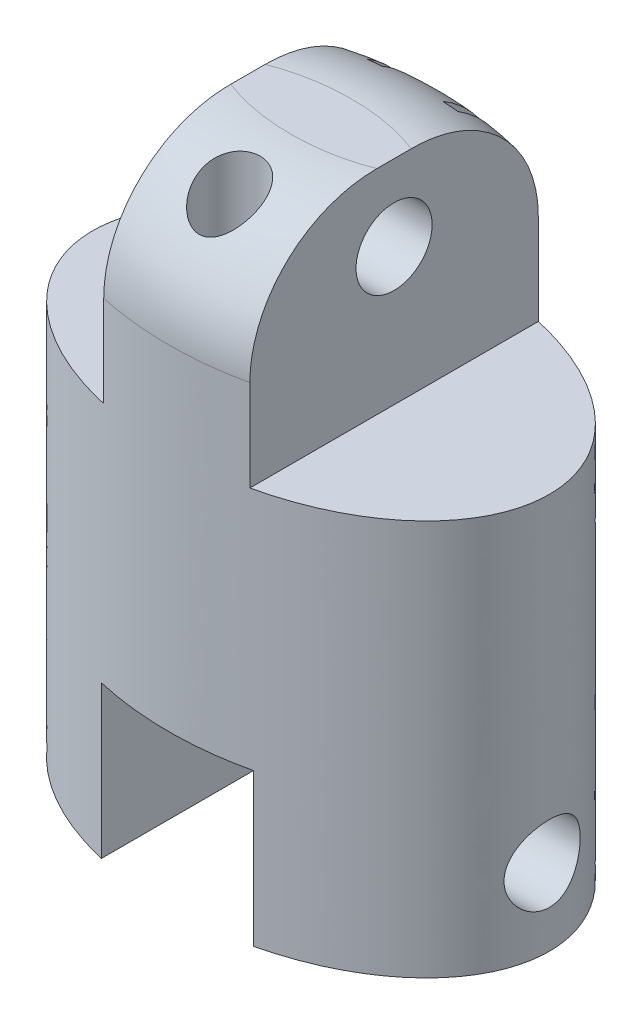
SolidWorks part; units mm, degrees
ref_plane "Front Plane" through (0, 0, 0) normal (0, 0, 1) x (1, 0, 0)
ref_plane "Top Plane" through (0, 0, 0) normal (0, 1, 0) x (1, 0, 0)
ref_plane "Right Plane" through (0, 0, 0) normal (1, 0, 0) x (0, 0, -1)
sketch "Sketch1" plane through (0, 0, 0) normal (0, 1, 0) x (1, 0, 0)
  circle A0 centre (0, -3.81) radius 1.27
  ellipse E0 centre (0, 0) end of major axis (-9.525, 0) minor radius 6.35
  dimension "D3" = 2.54
  dimension "D4" = 2.54
  dimension "D1" = 12.7
  dimension "D2" = 19.05
extrude "Boss-Extrude1" add sketch "Sketch1" along normal blind 25.4
sketch "Sketch2" plane through (0, 0, 0) normal (0, 0, 1) x (1, 0, 0)
  line L0 (-9.525, 12.7) -> (9.525, 12.7) construction
  line L1 (-9.525, 25.4) -> (-9.525, 0) construction
  line L2 (9.525, 0) -> (9.525, 25.4) construction
  line L3 (0, 25.4) -> (0, 0) construction
  line L4 (1.27, 25.4) -> (-1.27, 25.4) construction
  line L5 (9.525, 25.4) -> (-9.525, 25.4) construction
  line L10 (3.048, 16.51) -> (3.048, 25.4)
  line L11 (-3.175, 0) -> (3.175, 0)
  line L12 (-3.048, 16.51) -> (-3.048, 25.4)
  line L13 (-9.525, 16.51) -> (-3.048, 16.51)
  line L14 (-9.525, 16.51) -> (-9.525, 25.4)
  line L15 (-9.525, 25.4) -> (-3.048, 25.4)
  line L16 (9.525, 16.51) -> (9.525, 25.4)
  line L17 (3.048, 25.4) -> (9.525, 25.4)
  line L24 (-3.175, 0) -> (-3.175, 6.35)
  line L25 (-3.175, 6.35) -> (3.175, 6.35)
  line L26 (3.175, 0) -> (3.175, 6.35)
  line L28 (0, 0) -> (3.175, 6.35) construction
  line L30 (3.048, 16.51) -> (9.525, 16.51)
  line L31 (-3.175, 6.35) -> (0, 0) construction
  point P11 (0, 12.7)
  point P18 (0, 22.352)
  dimension "D1" = 6.096
  dimension "D2" = 6.35
  dimension "D3" = 8.89
  dimension "D4" = 6.35
  dimension "D5" = 8.89
extrude "Cut-Extrude1" cut sketch "Sketch2" against normal mid plane 25.4 contours L15 L14 L13 L12 | L10 L30 L16 L15 | L11 region at (6.2865, 20.955, 0) region at (0, 3.175, 0) region at (-6.2865, 20.955, 0)
sketch "Sketch3" plane through (3.048, 0, 0) normal (1, 0, 0) x (0, 0, -1)
  line L0 (0, 24.0964) -> (0, 2.7556) construction
  line L1 (6.0161, 25.4) -> (-6.0161, 25.4) construction
  circle A0 centre (0, 22.225) radius 1.5875
  circle A1 centre (0, 3.175) radius 1.5875
  dimension "D1" = 3.175
  dimension "D2" = 3.175
  dimension "D3" = 3.175
extrude "Cut-Extrude2" cut sketch "Sketch3" against normal mid plane 30.48
ref_plane "Plane1" through (0, 0, -6.35) normal (0, 0, 1) x (1, 0, 0)
fillet "Fillet1" radius 5.08 2 edges at (0, 25.4, -6.35) (0, 25.4, 6.35)
sketch "Sketch4" plane through (0, 0, -6.35) normal (0, 0, 1) x (1, 0, 0)
  line L0 (0, 2.3727) -> (0, 29.2896) construction
  line L3 (1.27, -2.2043) -> (1.905, -2.2043)
  line L4 (-1.905, -2.2043) -> (-1.27, -2.2043)
  line L5 (-1.905, -2.2043) -> (-1.905, 27.7382)
  line L6 (-1.905, 27.7382) -> (-1.27, 27.7382)
  line L7 (1.905, -2.2043) -> (1.905, 27.7382)
  line L8 (-1.905, -2.2043) -> (1.905, 27.7382) construction
  line L9 (-1.905, 27.7382) -> (1.905, -2.2043) construction
  line L11 (-1.27, -2.2043) -> (-1.27, 27.7382)
  line L13 (1.27, -2.2043) -> (1.27, 27.7382)
  line L14 (-1.27, -2.2043) -> (1.27, 27.7382) construction
  line L15 (-1.27, 27.7382) -> (1.27, -2.2043) construction
  line L16 (1.27, 27.7382) -> (1.905, 27.7382)
  point P2 (0, 0)
  point P6 (0, 12.7669)
  point P11 (0, 12.7669)
  dimension "D1" = 3.81
  dimension "D2" = 2.54
extrude "Cut-Extrude3" cut sketch "Sketch4" along normal blind 2.54
sketch "Sketch5" plane through (0, 0, 0) normal (0, 1, 0) x (1, 0, 0)
  line L0 (-3.175, 0) -> (3.175, 0)
  line L2 (-3.175, 0) -> (-3.175, 7.62)
  line L3 (-3.175, 7.62) -> (3.175, 7.62)
  line L4 (3.175, 0) -> (3.175, 7.62)
  line L5 (0, 0) -> (3.175, 7.62) construction
  line L6 (-3.175, 7.62) -> (0, 0) construction
  point P0 (0, 0)
  dimension "D1" = 6.35
  dimension "D2" = 7.62
revolve "Cut-Revolve2" cut sketch "Sketch5" angle 360 about L0
